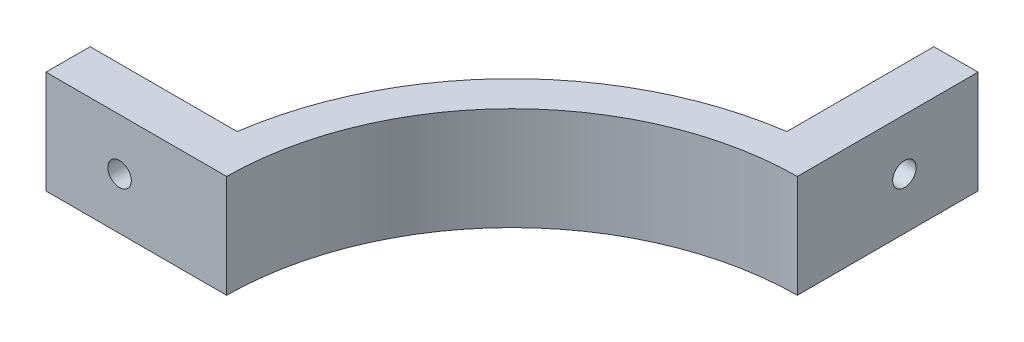
SolidWorks part; units mm, degrees
ref_plane "Front Plane" through (0, 0, 0) normal (0, 0, 1) x (1, 0, 0)
ref_plane "Top Plane" through (0, 0, 0) normal (0, 1, 0) x (1, 0, 0)
ref_plane "Right Plane" through (0, 0, 0) normal (1, 0, 0) x (0, 0, -1)
sketch "Sketch1" plane through (0, 0, 0) normal (0, 1, 0) x (1, 0, 0)
  line L0 (-3.1, 31.7805) -> (-3.1, 21.7805)
  line L1 (-0.1, 31.7805) -> (-0.1, 19.4997)
  line L2 (-0.1, 31.7805) -> (-3.1, 31.7805)
  line L3 (-21.7805, 3.1) -> (-31.7805, 3.1)
  line L4 (-31.7805, 3.1) -> (-31.7805, 0.1)
  line L5 (-31.7805, 0.1) -> (-19.4997, 0.1)
  arc A0 (-0.1, 19.4997) -> (-19.4997, 0.1) centre (0, 0) ccw
  arc A1 (-3.1, 21.7805) -> (-21.7805, 3.1) centre (0, 0) ccw
  point P14 (0, 0)
  point P15 (0, 0)
  point P16 (1.5, 19.4422)
  point P17 (0, 0)
  point P18 (-19.4422, -1.5)
  dimension "D1" = 39
  dimension "D2" = 44
  dimension "D3" = 3
  dimension "D4" = 10
  dimension "D5" = 0.1
  dimension "D6" = 0.1
extrude "Boss-Extrude1" add sketch "Sketch1" along normal mid plane 7
sketch3d "3DSketch2"
  line L0 (-21.7805, -3.5, -3.1) -> (-31.7805, -3.5, -3.1) construction
  line L1 (-31.7805, 3.5, -3.1) -> (-31.7805, -3.5, -3.1) construction
  line L3 (-3.1, 3.5, -31.7805) -> (-3.1, -3.5, -31.7805) construction
  line L4 (-0.1, 3.5, -31.7805) -> (-0.1, -3.5, -31.7805) construction
  line L5 (-3.1, -3.5, -26.7805) -> (-0.1, -3.5, -26.7805) construction
  line L6 (-3.1, -3.5, -31.7805) -> (-3.1, -3.5, -21.7805) construction
  line L7 (-0.1, -3.5, -19.4997) -> (-0.1, -3.5, -31.7805) construction
  point P1 (-26.7805, 0, -3.1)
  point P4 (-26.7805, -3.5, -3.1)
  point P7 (-31.7805, 0, -3.1)
  point P9 (-0.1, 0, -26.7805)
  point P10 (0, 0, 0)
  point P14 (-3.1, 0, -31.7805)
  point P16 (-0.1, 0, -31.7805)
  point P22 (0, 0, 0)
hole_wizard "M2x0.4 Tapped Hole3" positions "3DSketch5" profile "Sketch8" tap size "M2x0.4" standard "ANSI Metric" end condition through all
sketch3d "3DSketch5"
  point P0 (-26.7805, 0, -3.1)
  point P3 (-26.7805, 0, -3.1)
  point P13 (-0.1, 0, -26.7805)
  point P16 (-0.1, 0, -26.7805)
sketch "Sketch8" plane through (-0.1, 0, -26.7805) normal (0, 1, 0) x (0, 0, -1)
  line L0 (0, 0) -> (0, 31.6805)
  line L1 (0, 31.6805) -> (0.8, 31.6805)
  line L2 (0.8, 31.6805) -> (0.8, 0)
  line L5 (0.8, 0) -> (0, 0)
  line L11 (0, -6.35) -> (0, 107.95) construction
  dimension "Thru Tap Drill Dia." = 1.6
  dimension "Thru Tap Drill Depth" = 31.6805
cosmetic thread "Hole Thread31" parameters "D2"=2
cosmetic thread "Hole Thread32" parameters "D2"=2
